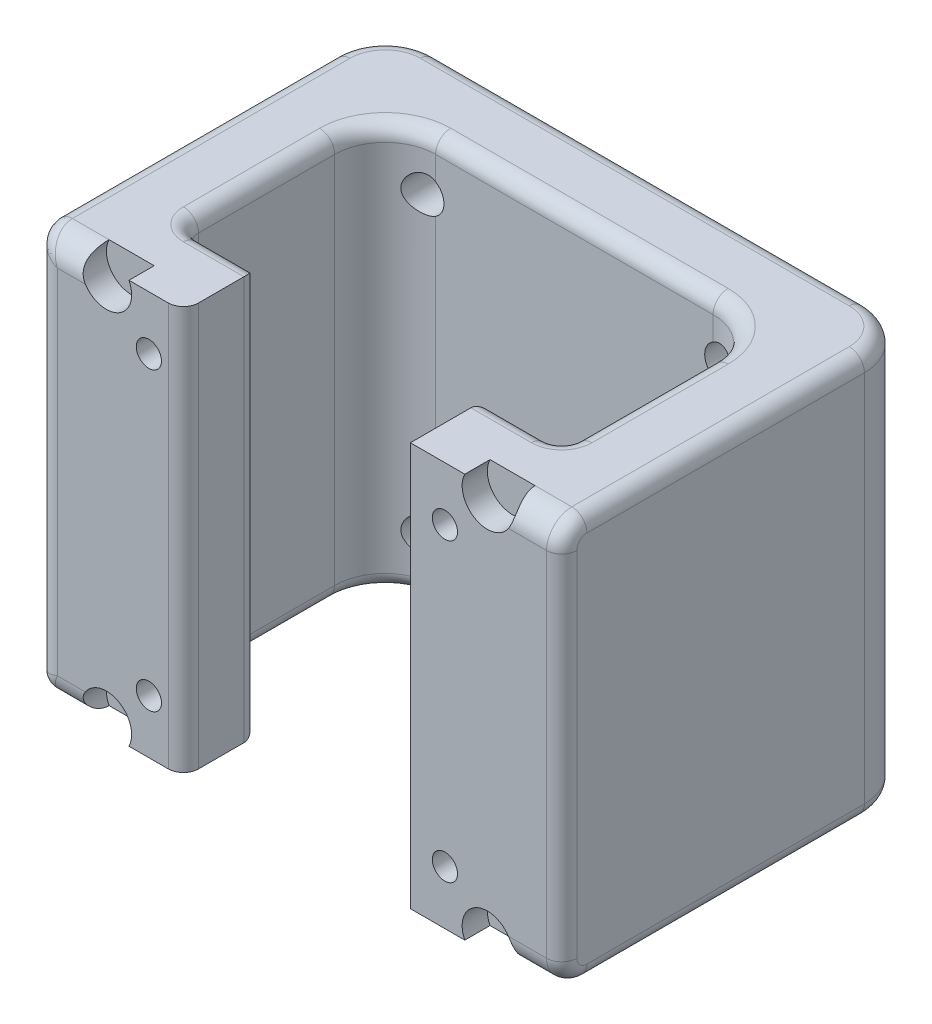
SolidWorks part; units mm, degrees
ref_plane "Front Plane" through (0, 0, 0) normal (0, 0, 1) x (1, 0, 0)
ref_plane "Top Plane" through (0, 0, 0) normal (0, 1, 0) x (1, 0, 0)
ref_plane "Right Plane" through (0, 0, 0) normal (1, 0, 0) x (0, 0, -1)
sketch "Sketch1" plane through (0, 0, 0) normal (0, 0, 1) x (1, 0, 0)
  line L1 (-52.5, 40) -> (52.5, 40)
  line L2 (-52.5, 40) -> (-52.5, -40)
  line L3 (-52.5, -40) -> (52.5, -40)
  line L4 (52.5, 40) -> (52.5, -40)
  line L5 (-52.5, 40) -> (52.5, -40) construction
  line L6 (-52.5, -40) -> (52.5, 40) construction
  point P0 (0, 0)
  dimension "D1" = 105
  dimension "D2" = 80
extrude "Boss-Extrude1" add sketch "Sketch1" along normal blind 15 contours L1 L4 L3 L2
sketch "Sketch2" plane through (0, 0, 15) normal (0, 0, 1) x (1, 0, 0)
  line L0 (-52.5, 40) -> (-52.5, -40)
  line L1 (-52.5, -40) -> (52.5, -40) construction
  line L2 (-52.5, 40) -> (-52.5, -40) construction
  line L3 (-52.5, -40) -> (-37.5, -40)
  line L4 (-37.5, -40) -> (-37.5, 40)
  line L5 (-52.5, 40) -> (52.5, 40) construction
  line L6 (-37.5, 40) -> (-52.5, 40)
  line L7 (52.5, 40) -> (37.5, 40)
  line L8 (37.5, 40) -> (37.5, -40)
  line L9 (37.5, -40) -> (52.5, -40)
  line L10 (52.5, -40) -> (52.5, 40)
  dimension "D1" = 15
  dimension "D2" = 15
extrude "Boss-Extrude2" add sketch "Sketch2" along normal blind 40
sketch "Sketch3" plane through (0, 0, 55) normal (0, 0, 1) x (1, 0, 0)
  line L0 (-52.5, 40) -> (-22.5, 40)
  line L1 (-37.5, 40) -> (37.5, 40) construction
  line L2 (-22.5, 40) -> (-22.5, -40)
  line L3 (-37.5, -40) -> (37.5, -40) construction
  line L4 (-22.5, -40) -> (-52.5, -40)
  line L5 (-52.5, -40) -> (-52.5, 40)
  line L6 (52.5, 40) -> (22.5, 40)
  line L7 (22.5, 40) -> (22.5, -40)
  line L8 (22.5, -40) -> (52.5, -40)
  line L9 (52.5, -40) -> (52.5, 40) construction
  line L10 (52.5, -40) -> (52.5, 40)
  dimension "D1" = 30
  dimension "D2" = 30
extrude "Boss-Extrude3" add sketch "Sketch3" along normal blind 15
sketch "Sketch5" plane through (0, 0, 0) normal (0, 0, -1) x (-1, 0, 0)
  circle A2 centre (29.3449, 29.3449) radius 3.5
  circle A4 centre (29.3449, -29.3449) radius 3.5
  circle A6 centre (-29.3449, -29.3449) radius 3.5
  circle A8 centre (-29.3449, 29.3449) radius 3.5
  point P22 (0, 0)
extrude "Cut-Extrude1" cut sketch "Sketch5" against normal blind 15
sketch "Sketch6" plane through (0, 0, 55) normal (0, 0, -1) x (-1, 0, 0)
  circle A0 centre (29.3449, 29.3449) radius 2.5
  circle A2 centre (29.3449, -29.3449) radius 2.5
  circle A3 centre (-29.3449, -29.3449) radius 2.5
  circle A4 centre (-29.3449, 29.3449) radius 2.5
  point P15 (0, 0)
  dimension "D1" = 5
  dimension "D2" = 4
extrude "Cut-Extrude2" cut sketch "Sketch6" against normal blind 15
sketch "Sketch7" plane through (0, 0, 70) normal (0, 0, 1) x (1, 0, 0)
  circle A11 centre (37.7595, -37.7595) radius 5
  circle A13 centre (-37.7595, -37.7595) radius 5
  circle A15 centre (-37.7595, 37.7595) radius 5
  circle A17 centre (37.7595, 37.7595) radius 5
  point P21 (0, 0)
  point P22 (0, 0)
extrude "Cut-Extrude3" cut sketch "Sketch7" against normal blind 5
fillet "Fillet1" radius 10 4 edges at (52.5, 0, 0) (-52.5, 0, 0) (37.5, 0, 15) (-37.5, 0, 15)
fillet "Fillet2" radius 3 30 edges at (30, -40, 55) (30, 40, 55) (-30, -40, 55) (-30, 40, 55) (37.5, -40, 40) (34.5711, -40, 17.9289) (0, -40, 15) (-34.5711, -40, 17.9289) (52.5, -40, 40) (49.5711, -40, 2.9289) (0, -40, 0) (-49.5711, -40, 2.9289) (52.5, 40, 40) (49.5711, 40, 2.9289) (0, 40, 0) (-49.5711, 40, 2.9289) (37.5, 40, 40) (34.5711, 40, 17.9289) (0, 40, 15) (-34.5711, 40, 17.9289) (-22.5, 0, 70) (52.5, 0, 70) (22.5, 0, 55) (-22.5, 0, 55) (-37.5, -40, 40) (-52.5, -40, 40) (-52.5, 40, 40) (-37.5, 40, 40) (-37.5, 0, 55) (37.5, 0, 55)
fillet "Fillet3" radius 5 9 edges at (51.6213, 39.1213, 69.1213) (51.6213, -39.1213, 69.1213) (45.8647, -40, 70) (45.8647, 40, 70) (-45.8647, 40, 70) (-51.6213, 39.1213, 70) (-52.5, 0, 70) (-45.8647, -40, 70) (-51.6213, -39.1213, 70)
